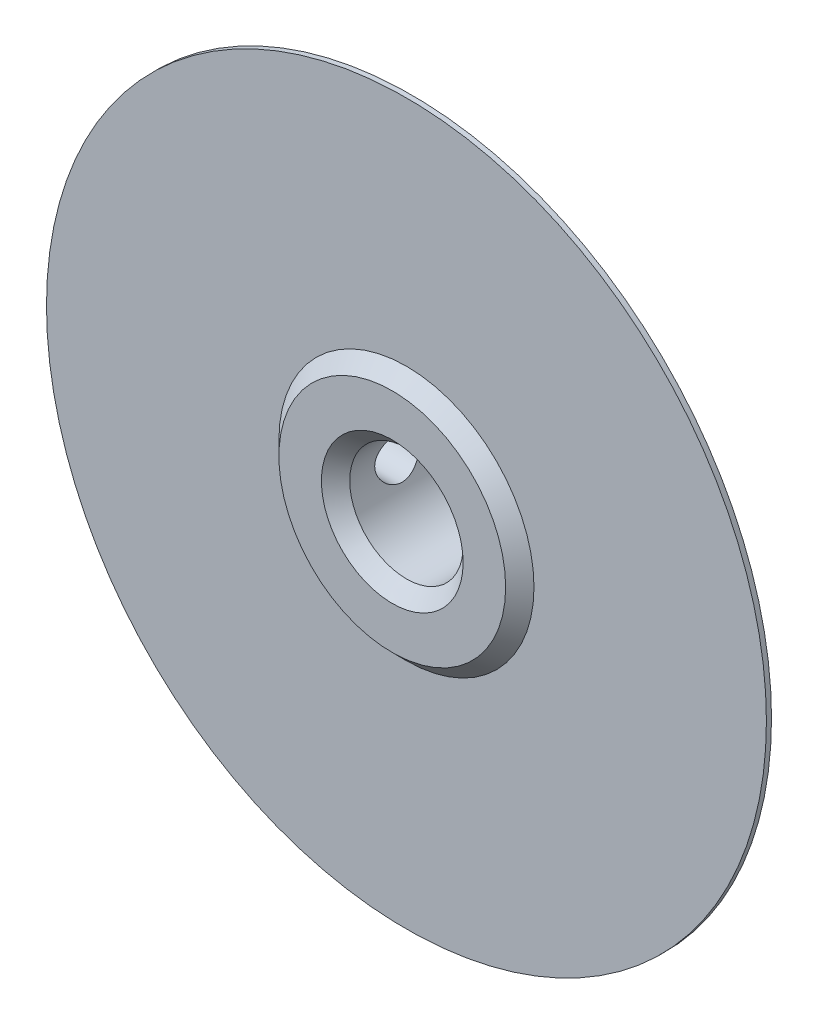
SolidWorks part; units mm, degrees
ref_plane "前视基准面" through (0, 0, 0) normal (0, 0, 1) x (1, 0, 0)
ref_plane "上视基准面" through (0, 0, 0) normal (0, 1, 0) x (1, 0, 0)
ref_plane "右视基准面" through (0, 0, 0) normal (1, 0, 0) x (0, 0, -1)
sketch "草图1" plane through (0, 0, 0) normal (0, 0, 1) x (1, 0, 0)
  circle A0 centre (0, 0) radius 12.7
  circle A1 centre (0, 0) radius 2
  dimension "D1" = 25.4
  dimension "D2" = 4
extrude "凸台-拉伸1" add sketch "草图1" along normal blind 0.18
sketch "草图2" plane through (0, 0, 0) normal (0, 0, -1) x (-1, 0, 0)
  line L0 (0, 3.6) -> (0, 2) construction
  circle A0 centre (0, 0) radius 2
  circle A1 centre (0, 0) radius 3.6
  dimension "D2" = 4
  dimension "D1" = 1.6
extrude "凸台-拉伸2" add sketch "草图2" along normal blind 3
sketch "草图3" plane through (0, 0, 0) normal (1, 0, 0) x (0, 0, -1)
  line L0 (3, 0) -> (0, 0) construction
  line L1 (3, -3.6) -> (3, 3.6) construction
  circle A0 centre (1.5, 0) radius 0.8
  dimension "D1" = 1.6
extrude "切除-拉伸1" cut sketch "草图3" against normal blind 10
cosmetic thread "装饰螺纹线1" parameters "D2"=2
chamfer "倒角1" distance 0.5 angle 45 2 edges at (-2, 0, -3) (-3.6, 0, -3)
sketch "草图4" plane through (0, 0, 0.18) normal (0, 0, 1) x (1, 0, 0)
  circle A0 centre (0, 0) radius 4.5
  circle A1 centre (0, 0) radius 2
  dimension "D1" = 9
extrude "凸台-拉伸3" add sketch "草图4" along normal blind 0.5
chamfer "倒角2" distance 0.5 angle 45 1 edges at (4.5, 0, 0.68)
chamfer "倒角3" distance 0.5 angle 45 1 edges at (2, 0, 0.68)
